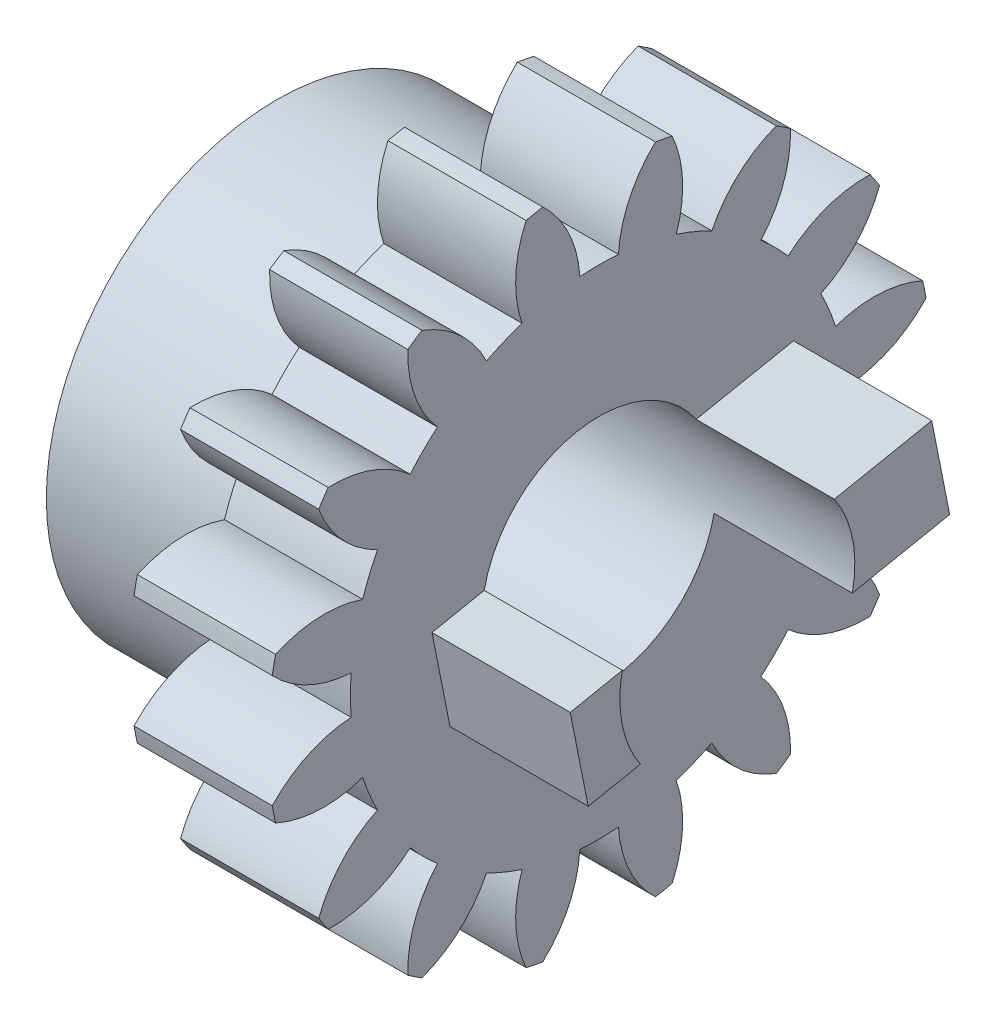
SolidWorks part; units mm, degrees
ref_plane "Plane1" through (0, 0, 0) normal (0, 0, 1) x (1, 0, 0)
ref_plane "Plane2" through (0, 0, 0) normal (0, 1, 0) x (1, 0, 0)
ref_plane "Plane3" through (0, 0, 0) normal (1, 0, 0) x (0, 0, -1)
other "Configuration Table"
sketch "HoldingSke" plane through (0, 0, 0) normal (0, 1, 0) x (1, 0, 0)
  line L0 (0, 0) -> (1.2016, -0.3445)
  line L1 (-15, 0) -> (100, 0) construction
  line L2 (0, 0) -> (-2.1039, 2.3779)
  line L3 (0, 0) -> (-11.863, 4.5341)
  line L4 (0, 0) -> (8.3015, 2.3804)
  line L5 (0, 0) -> (-46.8476, -17.4728)
  line L6 (0, 0) -> (-2.4869, -1.6779)
  line L7 (-2.1039, 2.3779) -> (8.6586, 51.2059)
  line L8 (-76.2, 54.61) -> (-76.1, 54.61)
  line L9 (-71.009, 38.7566) -> (-53.1078, 45.2721)
  line L10 (-76.2, 71.12) -> (104.1128, 71.12)
  line L11 (0, 0) -> (-3, 0)
  line L12 (-76.2, 101.6) -> (-76.17, 101.6)
  line L13 (24.9733, 27.94) -> (52.9518, 28.4284)
  line L14 (24.9733, 27.94) -> (24.9743, 27.94)
  line L15 (24.9733, 27.94) -> (100.4006, 29.5858)
  line L16 (-63.627, -0.8) -> (-12.827, -0.8)
  circle A0 centre (0, 0) radius 0.5
  circle A1 centre (0, 0) radius 5.399
  circle A2 centre (0, 0) radius 37.5
  circle A3 centre (0, 0) radius 0.5
  dimension "MHD" = 10.798
  dimension "Hub_dia" = 75
  dimension "Bore" = 1
  dimension "MBD" = 1
  dimension "Num_teeth" = 16
  dimension "Pitch" = 1.25
  dimension "Overall_len" = 50
  dimension "Show_teeth" = 16
  dimension "Thickness" = 3
  dimension "OAL" = 50.0001
  dimension "T_dim" = 0.1
  dimension "Ap" = 20
  dimension "H" = 19.05
  dimension "Pitch_radius" = 180.3128
  dimension "Width" = 3
  dimension "Backlash" = 0.03
  dimension "Addendum_fac" = 1
  dimension "Dedendum_fac" = 1.25
  dimension "Clearance_fac" = 0.25
  dimension "Dedendum_add" = 0.001
  dimension "Module" = 0.8
sketch "BasProSke" plane through (0, 0, 0) normal (0, 1, 0) x (1, 0, 0)
  line L0 (-10, 0) -> (60, 0) construction
  line L1 (0, 0) -> (0, 7.2)
  line L2 (0, 0) -> (3, 0)
  line L3 (3, 0) -> (3, 7.2)
  line L4 (3, 7.2) -> (0, 7.2)
  dimension "Thickness" = 3
  dimension "Diameter" = 14.4
revolve "Base-Revolve" add sketch "BasProSke" angle 360 about L0
sketch "TooCutSke" plane through (0, 0, 0) normal (1, 0, 0) x (0, 0, -1)
  line L1 (0, 0) -> (0, 107) construction
  line L2 (0, 0) -> (-0.6798, 6.3638) construction
  line L3 (0, 0) -> (-2.4871, 12.5033) construction
  line L4 (-0.6798, 6.3638) -> (-1.2435, 6.2517) construction
  arc A0 (0.4184, 5.3828) -> (-0.4184, 5.3828) centre (0, 0) ccw
  arc A1 (1.2466, 7.117) -> (-1.2466, 7.117) centre (0, 0) ccw
  circle A2 centre (0, 0) radius 6.4 construction
  circle A3 centre (0, 0) radius 6.014 construction
  arc A4 (-0.4184, 5.3828) -> (-1.2466, 7.117) centre (-2.9737, 5.2274) ccw
  arc A5 (1.2466, 7.117) -> (0.4184, 5.3828) centre (2.9737, 5.2274) ccw
  dimension "Root_dia" = 10.798
  dimension "Overcut_dia" = 14.4508
  dimension "Pitch_dia" = 12.8
  dimension "Base_dia" = 12.0281
  dimension "Flank_rad" = 2.56
  dimension "Half_ang" = 11.25
  dimension "Half_CT" = 0.5748
extrude "ToothCut" cut sketch "TooCutSke" along normal through all
fillet "Breaks" [suppressed] radius 0.016 tangent propagation no
fillet "RootFillets" [suppressed] radius 0.201
pattern_circular "TeethCuts" count 16 over 360 about axis through (-10, 0, 0) along (1, 0, 0) of "ToothCut", "RootFillets", "Breaks"
sketch "HubNeaOneSke" plane through (0, 0, 0) normal (-1, 0, 0) x (0, 0, 1)
  circle A0 centre (0, 0) radius 5.399
  dimension "Diameter" = 10.798
extrude "HubNearOne" [suppressed] add sketch "HubNeaOneSke" along normal blind 47.0001
sketch "HubNeaBotSke" plane through (0, 0, 0) normal (-1, 0, 0) x (0, 0, 1)
  circle A0 centre (0, 0) radius 5.399
  dimension "Diameter" = 10.798
extrude "HubNearBoth" [suppressed] add sketch "HubNeaBotSke" along normal blind 23.5
ref_plane "FarPln" through (3, 0, 0) normal (1, 0, 0) x (0, 0, -1)
sketch "HubFarSke" plane through (3, 0, 0) normal (1, 0, 0) x (0, 0, -1)
  circle A0 centre (0, 0) radius 5.399
  dimension "Diameter" = 10.798
extrude "HubFar" [suppressed] add sketch "HubFarSke" along normal blind 23.5
sketch "BorSke" plane through (0, 0, 0) normal (1, 0, 0) x (0, 0, -1)
  circle A0 centre (0, 0) radius 0.5
  dimension "Diameter" = 1
extrude "Bore" cut sketch "BorSke" along normal mid plane 100.0001
sketch "KeySke" plane through (0, 0, 0) normal (1, 0, 0) x (0, 0, -1)
  line L0 (-0.05, 0) -> (-0.05, 0.6)
  line L1 (-0.05, 0.6) -> (0.05, 0.6)
  line L2 (0.05, 0.6) -> (0.05, 0)
  line L3 (0, 0) -> (0, 34) construction
  line L4 (-0.05, 0) -> (0.05, 0)
  dimension "Offset" = 0.6
extrude "Keyway" [suppressed] cut sketch "KeySke" along normal mid plane 100.0001
pattern_circular "Keyway2" [suppressed] count 2 every 90 about axis through (-10, 0, 0) along (1, 0, 0) reverse direction yes
ref_axis "基准轴1" through (0, 0, 0) along (1, 0, 0)
sketch "草图1" plane through (0, 0, 0) normal (1, 0, 0) x (0, 0, -1)
  circle A0 centre (0, 0) radius 2.55
  dimension "D1" = 5.1
extrude "切除-拉伸1" cut sketch "草图1" along normal through all
sketch "草图3" plane through (0, 0, 0) normal (-1, 0, 0) x (0, 0, 1)
  circle A0 centre (0, 0) radius 5
  circle A1 centre (0, 0) radius 2.55 construction
  circle A2 centre (0, 0) radius 2.55
  dimension "D1" = 10
extrude "凸台-拉伸2" add sketch "草图3" along normal blind 4 contours A0 A2 region at (0, 0, -4.8586)
sketch "草图2" plane through (3, 0, 0) normal (1, 0, 0) x (0, 0, -1)
  line L0 (4.4135, 0.8779) -> (0, 0) construction
  line L1 (5.1331, 1.6733) -> (5.3828, 0.4184) construction
  line L2 (4.2184, 1.8587) -> (4.6086, -0.1029)
  line L10 (0, 0) -> (-3.4327, -0.6828) construction
  line L11 (4.2184, 1.8587) -> (-3.6278, 0.298)
  line L12 (-3.6278, 0.298) -> (-3.2377, -1.6636)
  line L13 (-3.2377, -1.6636) -> (4.6086, -0.1029)
  circle A0 centre (0, 0) radius 2.55 construction
  circle A1 centre (0, 0) radius 2.55
  point P2 (5.258, 1.0459)
  point P7 (4.4135, 0.8779)
  point P18 (-3.4327, -0.6828)
  dimension "D1" = 2
  dimension "D4" = 3.5
  dimension "D5" = 4.5
extrude "凸台-拉伸1" add sketch "草图2" along normal blind 3 contours A1 L11 L12 L13 | A1 L13 L2 L11 region at (3, 0.681, -3.4235) region at (3, -0.5833, 2.9323)
equation "' \"Module@HoldingSke\" = 6.35"
equation "' \"Num_teeth@HoldingSke\" = 12"
equation "' \"Ap@HoldingSke\" =  20"
equation "' \"Ap@HoldingSke\" = 20"
equation "' \"Width@HoldingSke\" = 0.5 * 25.4"
equation "' \"Hub_dia@HoldingSke\"= 1 * 25.4"
equation "' \"Hub_dia@HoldingSke\" = 1 * 25.4"
equation "' \"Overall_len@HoldingSke\" = 1.0 * 25.4"
equation "' \"Bore@HoldingSke\" = 0.75 * 25.4"
equation "' \"T_dim@HoldingSke\" = 0.1 * 25.4"
equation "' \"Width@KeySke\" = 0.25 * 25.4"
equation "' \"Show_teeth@HoldingSke\" = 13"
equation "' \"Backlash@HoldingSke\" = 0.009 * 25.4"
equation "' \"Addendum_fac@HoldingSke\" = 1.0"
equation "' \"Dedendum_fac@HoldingSke\" = 1.25"
equation "' \"Dedendum_add@HoldingSke\" = 0.00005 * 25.4"
equation "' \"Clearance_fac@HoldingSke\" = 0.25"
equation "\"Pitch@HoldingSke\" = 1 / \"Module@HoldingSke\""
equation "\"Overcut_dia@TooCutSke\" = (\"Num_teeth@HoldingSke\" + 2 * \"Addendum_fac@HoldingSke\") / \"Pitch@HoldingSke\" + 0.002 * 25.4"
equation "\"Pitch_dia@TooCutSke\" = \"Num_teeth@HoldingSke\" / \"Pitch@HoldingSke\""
equation "\"Base_dia@TooCutSke\" = \"Num_teeth@HoldingSke\" / \"Pitch@HoldingSke\" * cos((\"Ap@HoldingSke\"  * 3.14159265 / 180))"
equation "\"Root_dia@TooCutSke\" = (\"Num_teeth@HoldingSke\" + 2) / \"Pitch@HoldingSke\" - 2 * (\"Addendum_fac@HoldingSke\" + \"Dedendum_fac@HoldingSke\") / \"Pitch@HoldingSke\" - \"Dedendum_add@HoldingSke\" * 2"
equation "\"Half_ang@TooCutSke\" = 180 / \"Num_teeth@HoldingSke\""
equation "\"Half_CT@TooCutSke\" = \"Num_teeth@HoldingSke\" / \"Pitch@HoldingSke\" * sin((3.14159265 / 2 / \"Num_teeth@HoldingSke\")) / 2 - 7 * \"Backlash@HoldingSke\" / 4"
equation "\"Flank_rad@TooCutSke\" = \"Num_teeth@HoldingSke\" / \"Pitch@HoldingSke\" / 5"
equation "\"Radius@RootFillets\" = \"Clearance_fac@HoldingSke\" / \"Pitch@HoldingSke\" + \"Dedendum_add@HoldingSke\""
equation "\"Break_rad@Breaks\" = 0.02 / \"Pitch@HoldingSke\""
equation "\"Thickness@HoldingSke\" = \"Width@HoldingSke\""
equation "\"OAL@HoldingSke\" = \"Thickness@HoldingSke\""
equation "\"MHD@HoldingSke\" = (\"Num_teeth@HoldingSke\" + 2) / \"Pitch@HoldingSke\" - 2 * (\"Addendum_fac@HoldingSke\" + \"Dedendum_fac@HoldingSke\")  / \"Pitch@HoldingSke\" - \"Dedendum_add@HoldingSke\" * 2"
equation "\"MBD@HoldingSke\" = (\"Num_teeth@HoldingSke\" + 2) / \"Pitch@HoldingSke\" - 2 * (\"Addendum_fac@HoldingSke\" + \"Dedendum_fac@HoldingSke\")  / \"Pitch@HoldingSke\" - \"Dedendum_add@HoldingSke\" * 2 - 0.002 * 25.4"
equation "\"MHD@HoldingSke\" = ((sgn( \"MHD@HoldingSke\" - \"Hub_dia@HoldingSke\" )-1)*( \"MHD@HoldingSke\" - \"Hub_dia@HoldingSke\" ))/-2+ \"Hub_dia@HoldingSke\""
equation "\"MBD@HoldingSke\" = ((sgn( \"MBD@HoldingSke\" - \"Bore@HoldingSke\" )-1)*( \"MBD@HoldingSke\" - \"Bore@HoldingSke\" ))/-2+ \"Bore@HoldingSke\""
equation "\"OAL@HoldingSke\" = ((sgn( \"OAL@HoldingSke\" - \"Overall_len@HoldingSke\" )+1)*( \"OAL@HoldingSke\" - \"Overall_len@HoldingSke\" ))/2 + \"Overall_len@HoldingSke\" + 0.000002 * 25.4"
equation "\"Num_teeth@TeethCuts\" = int( \"Show_teeth@HoldingSke\" ) + 1"
equation "\"Num_teeth@TeethCuts\" = ((sgn( \"Num_teeth@TeethCuts\" - \"Num_teeth@HoldingSke\" )-1)*( \"Num_teeth@TeethCuts\" - \"Num_teeth@HoldingSke\" ))/-2+ \"Num_teeth@HoldingSke\""
equation "\"Num_teeth@TeethCuts\" = ((sgn( \"Num_teeth@TeethCuts\" - 2.0)+1)*( \"Num_teeth@TeethCuts\" - 2.0))/2 +2.0"
equation "\"Angle@TeethCuts\" = 360.0 / \"Num_teeth@HoldingSke\""
equation "\"Diameter@BasProSke\" = (\"Num_teeth@HoldingSke\" + 2 * \"Addendum_fac@HoldingSke\") / \"Pitch@HoldingSke\""
equation "\"Thickness@BasProSke\"  = \"Thickness@HoldingSke\""
equation "' \"Fillet_rad@BasProSke\" =  \"Thickness@HoldingSke\" * 0.05"
equation "' \"Fillet_rad@BasProSke\" = \"Thickness@HoldingSke\" * 0.05"
equation "\"MHD@HoldingSke\" = ((sgn( \"MHD@HoldingSke\" - \"Root_dia@TooCutSke\" )-1)*( \"MHD@HoldingSke\" - \"Root_dia@TooCutSke\" ))/-2+ \"Root_dia@TooCutSke\""
equation "\"Diameter@HubNeaOneSke\" = \"MHD@HoldingSke\""
equation "\"Length@HubNearOne\" = \"OAL@HoldingSke\" - \"Thickness@BasProSke\""
equation "\"Diameter@HubNeaBotSke\" = \"MHD@HoldingSke\""
equation "\"Length@HubNearBoth\" = ( \"OAL@HoldingSke\" - \"Thickness@BasProSke\" ) / 2.0"
equation "\"Thickness@FarPln\" = \"Thickness@BasProSke\""
equation "\"Diameter@HubFarSke\" = \"MHD@HoldingSke\""
equation "\"Length@HubFar\" = ( \"OAL@HoldingSke\" - \"Thickness@BasProSke\" ) / 2.0"
equation "\"Diameter@BorSke\" = \"MBD@HoldingSke\""
equation "\"D1@Bore\" = \"OAL@HoldingSke\" * 2.0"
equation "\"D1@Keyway\" = \"OAL@HoldingSke\" * 2.0"
equation "\"Offset@KeySke\" = \"T_dim@HoldingSke\" + \"MBD@HoldingSke\" / 2.0"
